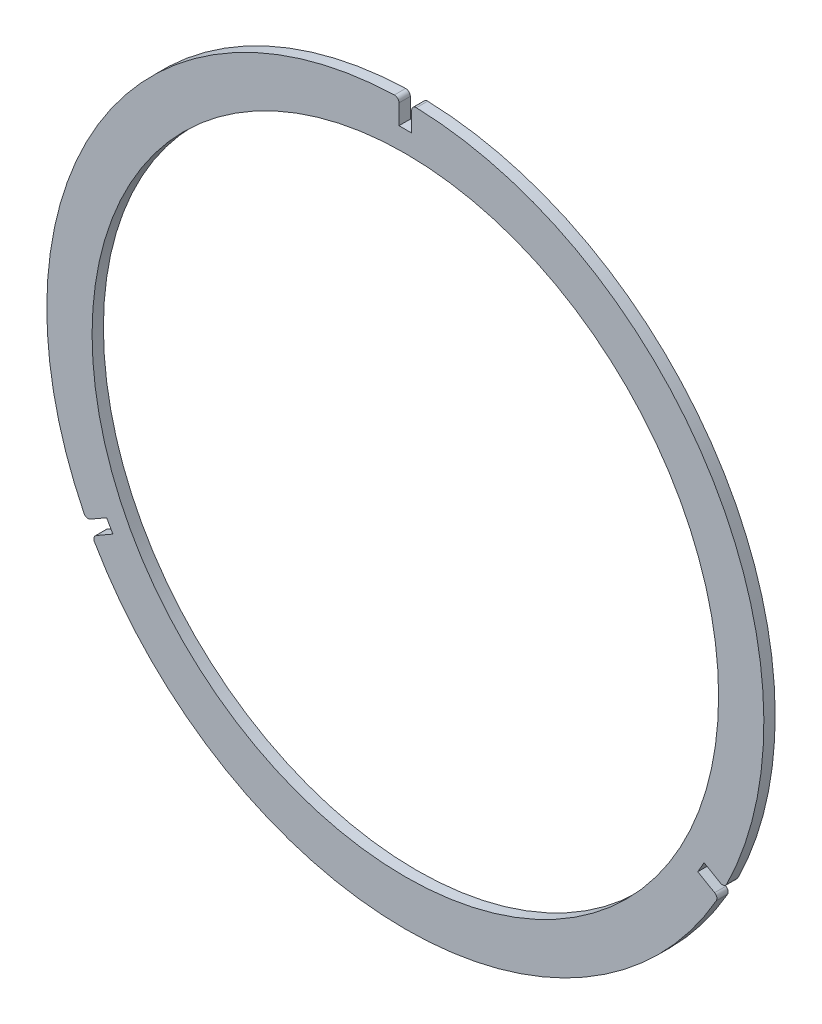
SolidWorks part; units mm, degrees
material "Balsa"
ref_plane "Front Plane" through (0, 0, 0) normal (0, 0, 1) x (1, 0, 0)
ref_plane "Top Plane" through (0, 0, 0) normal (0, 1, 0) x (1, 0, 0)
ref_plane "Right Plane" through (0, 0, 0) normal (1, 0, 0) x (0, 0, -1)
sketch "Sketch2" plane through (0, 0, 0) normal (0, 0, 1) x (1, 0, 0)
  line L0 (0, 0) -> (0, 240.9936) construction
  line L1 (-1.7839, 106.6642) -> (-1.7839, 99.822)
  line L2 (1.7839, 106.6642) -> (1.7839, 99.822)
  line L3 (-1.7839, 99.822) -> (1.7839, 99.822)
  line L4 (-87.7705, -42.8471) -> (-87.8712, -42.9053)
  line L5 (-604.1774, -338.907) -> (0, 9.8743) construction
  line L6 (-89.5483, -39.7674) -> (-83.8289, -36.4657)
  line L7 (-87.7705, -42.8471) -> (-82.0511, -39.5454)
  line L8 (-83.8289, -36.4657) -> (-82.0511, -39.5454)
  line L9 (604.1774, -338.907) -> (0, 9.8743) construction
  line L10 (87.7705, -42.8471) -> (82.0511, -39.5454)
  line L11 (87.7705, -42.8471) -> (87.8712, -42.9053)
  line L12 (89.5483, -39.7674) -> (83.8289, -36.4657)
  line L13 (83.8289, -36.4657) -> (82.0511, -39.5454)
  arc A0 (-7.652, 93.6463) -> (7.652, 93.6463) centre (0, 6.0782) ccw
  arc A1 (-1.7839, 106.6642) -> (-89.5483, -39.7674) centre (0, 6.0782) ccw
  arc A6 (-1.778, 93.962) -> (-7.652, 93.6463) centre (0, 6.0782) ccw
  circle A7 centre (0, 6.0782) radius 87.9018 construction
  arc A8 (0, 93.98) -> (-1.778, 93.962) centre (0, 6.0782) ccw
  arc A9 (1.778, 93.962) -> (0, 93.98) centre (0, 6.0782) ccw
  arc A10 (1.778, 93.962) -> (0, 93.98) centre (0, 6.0782) ccw construction
  arc A12 (7.652, 93.6463) -> (1.778, 93.962) centre (0, 6.0782) ccw
  arc A13 (0, 93.98) -> (-1.778, 93.962) centre (0, 6.0782) ccw construction
  arc A15 (7.652, 93.6463) -> (1.778, 93.962) centre (0, 6.0782) ccw construction
  arc A16 (-1.778, 93.962) -> (-7.652, 93.6463) centre (0, 6.0782) ccw construction
  arc A17 (0, 106.68) -> (-1.7839, 106.6642) centre (0, 6.0782) ccw construction
  circle A18 centre (0, 6.0782) radius 100.6018 construction
  arc A19 (1.7839, 106.6642) -> (0, 106.68) centre (0, 6.0782) ccw construction
  arc A20 (-87.8712, -42.9053) -> (87.8712, -42.9053) centre (0, 6.0782) ccw
  arc A21 (-89.5483, -39.7674) -> (-88.7234, -41.3442) centre (0, 6.0782) ccw construction
  arc A22 (-88.7234, -41.3442) -> (-87.8712, -42.9053) centre (0, 6.0782) ccw construction
  arc A23 (87.8712, -42.9053) -> (88.7234, -41.3442) centre (0, 6.0782) ccw construction
  arc A24 (89.5483, -39.7674) -> (1.7839, 106.6642) centre (0, 6.0782) ccw
  arc A25 (88.7234, -41.3442) -> (89.5483, -39.7674) centre (0, 6.0782) ccw construction
  point P25 (0, 99.822)
  dimension "D3" = 119.997
  dimension "D8" = 12.7
  dimension "D6" = 87.9018
  dimension "D2" = 1.7839
  dimension "D4" = 9.8743
  dimension "D5" = 3.556
  dimension "D1" = 93.98
  dimension "D7" = 5.842
  dimension "D9" = 6.604
  dimension "D10" = 3.556
extrude "Boss-Extrude1" add sketch "Sketch2" against normal blind 3.175
fillet "Fillet2" radius 1.27 6 edges at (-1.7839, 106.6642, -1.5875) (-87.8712, -42.9053, -1.5875) (-89.5483, -39.7674, -1.5875) (89.5483, -39.7674, -1.5875) (87.8712, -42.9053, -1.5875) (1.7839, 106.6642, -1.5875)
